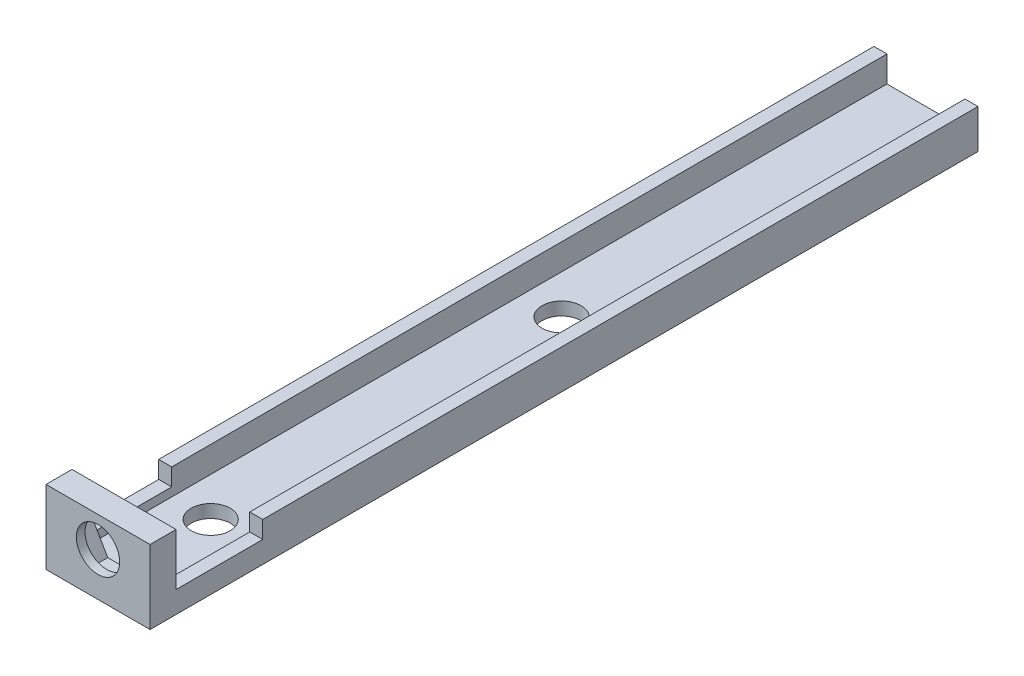
SolidWorks part; units mm, degrees
ref_plane "Front Plane" through (0, 0, 0) normal (0, 0, 1) x (1, 0, 0)
ref_plane "Top Plane" through (0, 0, 0) normal (0, 1, 0) x (1, 0, 0)
ref_plane "Right Plane" through (0, 0, 0) normal (1, 0, 0) x (0, 0, -1)
sketch "Sketch1" plane through (0, 0, 0) normal (0, 0, 1) x (1, 0, 0)
  line L0 (0, 0) -> (0, 9)
  line L1 (0, 9) -> (3, 9)
  line L2 (3, 9) -> (3, 3)
  line L3 (3, 3) -> (21, 3)
  line L4 (21, 3) -> (21, 9)
  line L5 (21, 9) -> (24, 9)
  line L6 (24, 9) -> (24, 0)
  line L7 (24, 0) -> (0, 0)
  line L8 (3, 3) -> (3, 0) construction
  dimension "D1" = 6
  dimension "D2" = 3
  dimension "D3" = 18
extrude "Boss-Extrude1" add sketch "Sketch1" along normal blind 165
sketch "Sketch2" plane through (0, 0, 165) normal (0, 0, 1) x (1, 0, 0)
  line L0 (0, 0) -> (24, 0)
  line L1 (24, 0) -> (24, 5)
  line L2 (24, 0) -> (24, 9) construction
  line L3 (24, 5) -> (21, 5)
  line L4 (21, 9) -> (21, 3) construction
  line L5 (21, 5) -> (21, 3)
  line L6 (21, 3) -> (3, 3)
  line L7 (3, 3) -> (3, 5)
  line L8 (3, 3) -> (3, 9) construction
  line L9 (3, 5) -> (0, 5)
  line L11 (0, 5) -> (0, 0)
  dimension "D1" = 2
extrude "Boss-Extrude2" add sketch "Sketch2" along normal blind 24
sketch "Sketch3" plane through (0, 0, 189) normal (0, 0, 1) x (1, 0, 0)
  line L1 (0, 0) -> (24, 0)
  line L2 (0, 0) -> (0, 17)
  line L3 (0, 17) -> (24, 17)
  line L4 (24, 0) -> (24, 17)
  line L5 (12, 10) -> (0, 10) construction
  line L6 (15.7528, 16.5) -> (8.2472, 16.5)
  line L7 (8.2472, 16.5) -> (4.4944, 10)
  line L8 (4.4944, 10) -> (8.2472, 3.5)
  line L9 (8.2472, 3.5) -> (15.7528, 3.5)
  line L10 (15.7528, 3.5) -> (19.5056, 10)
  line L11 (19.5056, 10) -> (15.7528, 16.5)
  line L12 (12, 10) -> (12, 17) construction
  line L13 (21, 3) -> (3, 3) construction
  circle A0 centre (12, 10) radius 5
  circle A1 centre (12, 10) radius 6.5 construction
  line M7 (0, 5) -> (0, 0)
  line M8 (0, 0) -> (24, 0)
  line M9 (24, 0) -> (24, 5)
  line M10 (24, 5) -> (21, 5)
  line M11 (21, 5) -> (21, 3)
  line M12 (21, 3) -> (3, 3)
  line M13 (3, 3) -> (3, 5)
  line M14 (3, 5) -> (0, 5)
  dimension "D2" = 10
  dimension "D1" = 17
  dimension "D3" = 13
extrude "Boss-Extrude3" add sketch "Sketch3" against normal blind 4 contours L4 L3 L2 L11 L10 L9 L8 L7 L6 M10 M14 M13 M12 M11 region at (0.2778, 11, 189)
extrude "Boss-Extrude4" add sketch "Sketch3<3>" along normal blind 2 contours L4 L3 L2 L11 L10 L9 L8 L7 L6 M10 M14 M13 M12 M11 | M14 M7 M8 M9 M10 M11 M12 M13 | L10 L11 L6 L7 L8 L9 A0 region at (12, 1.8571, 189) region at (0.2778, 11, 189) region at (17.4572, 13.1507, 189)
sketch "Sketch3<3>" plane through (0, 0, 189) normal (0, 0, 1) x (1, 0, 0) same geometry as "Sketch3"
sketch "Sketch4" plane through (0, 3, 0) normal (0, 1, 0) x (1, 0, 0)
  line L0 (21, -185) -> (3, -185) construction
  line L1 (12, -165) -> (12, -84.075) construction
  line L2 (3, -185) -> (3, 0) construction
  line L3 (21, -185) -> (21, 0) construction
  circle A0 centre (12, -165) radius 4.5
  circle A1 centre (12, -84.075) radius 4.5
  dimension "D2" = 9
  dimension "D1" = 80.925
  dimension "D3" = 20
extrude "Cut-Extrude1" cut sketch "Sketch4" against normal through all
